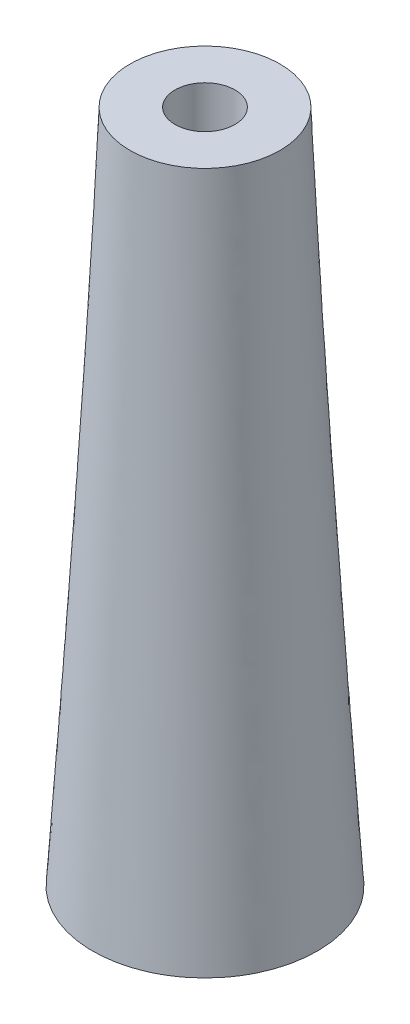
SolidWorks part; units mm, degrees
ref_plane "Alzado" through (0, 0, 0) normal (0, 0, 1) x (1, 0, 0)
ref_plane "Planta" through (0, 0, 0) normal (0, 1, 0) x (1, 0, 0)
ref_plane "Vista lateral" through (0, 0, 0) normal (1, 0, 0) x (0, 0, -1)
sketch "Croquis2" plane through (0, 0, 0) normal (0, 1, 0) x (1, 0, 0)
  circle A0 centre (0, 0) radius 75
  point P4 (-371.2073, -98.7182)
ref_plane "Plano1" through (0, 450, 0) normal (0, 1, 0) x (1, 0, 0)
sketch "Croquis3" plane through (0, 450, 0) normal (0, 1, 0) x (1, 0, 0)
  circle A0 centre (0, 0) radius 50
loft "Recubrir2" add section "Croquis3" section "Croquis2" connector at (16.9073, 450, 47.0547) connector at (52.6316, 0, 53.4314)
sketch "Croquis4" plane through (0, 450, 0) normal (0, 1, 0) x (1, 0, 0)
  circle A0 centre (0, 0) radius 20
extrude "Cortar-Extruir1" cut sketch "Croquis4" against normal blind 529 and the other way blind 40
